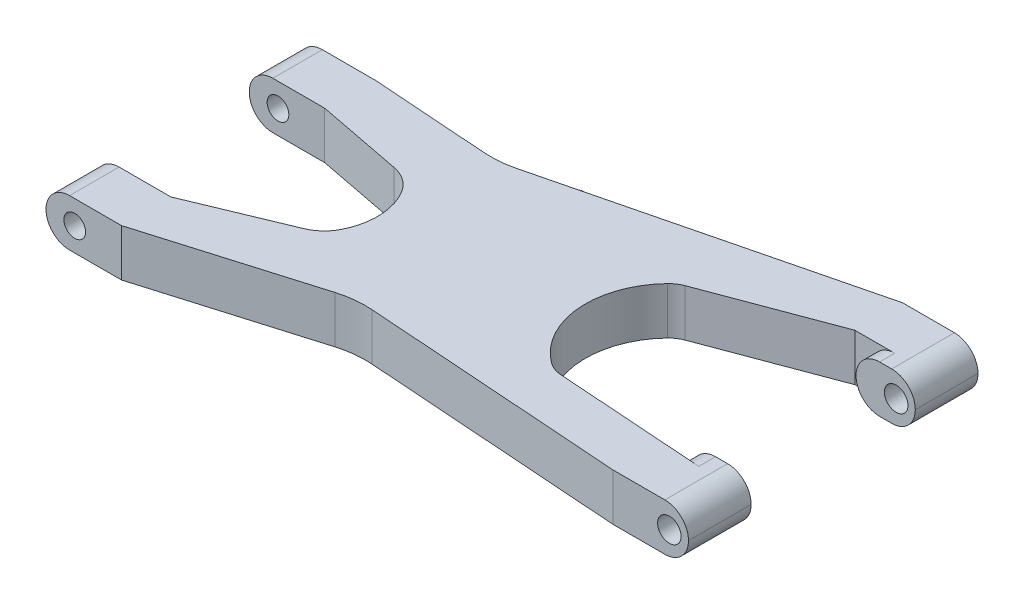
SolidWorks part; units mm, degrees
ref_plane "Front Plane" through (0, 0, 0) normal (0, 0, 1) x (1, 0, 0)
ref_plane "Top Plane" through (0, 0, 0) normal (0, 1, 0) x (1, 0, 0)
ref_plane "Right Plane" through (0, 0, 0) normal (1, 0, 0) x (0, 0, -1)
sketch "Sketch1" plane through (0, 0, 0) normal (0, 1, 0) x (1, 0, 0)
  line L0 (0, 0) -> (0, 38.989)
  line L1 (-81.915, 29.4386) -> (-71.628, 29.4386)
  line L2 (-81.915, 29.4386) -> (-81.915, -4.5974)
  line L3 (0, 0) -> (-10.16, 0)
  line L4 (-71.628, 29.4386) -> (-10.16, 38.989)
  line L5 (0, 38.989) -> (-10.16, 38.989)
  line L6 (-71.755, -4.5974) -> (-10.16, 0)
  line L8 (-81.915, -4.5974) -> (-71.755, -4.5974)
  dimension "D1" = 38.989
  dimension "D2" = 34.036
  dimension "D3" = 81.915
  dimension "D4" = 9.5504
  dimension "D5" = 4.5974
  dimension "D6" = 61.468
  dimension "D7" = 10.16
  dimension "D8" = 10.16
  dimension "D9" = 10.16
  dimension "D10" = 61.595
extrude "Boss-Extrude1" add sketch "Sketch1" along normal blind 6.35
fillet "Fillet2" radius 3.175 4 edges at (0, 0, -19.4945) (0, 6.35, -19.4945) (-81.915, 0, -12.4206) (-81.915, 6.35, -12.4206)
sketch "Sketch2" plane through (-0.605, 0, 0) normal (0, 0, -1) x (-1, 0, 0)
  circle A0 centre (1.9663, 3.175) radius 1.5875
  circle A1 centre (77.4406, 3.175) radius 1.4605
  dimension "D1" = 2.921
  dimension "D2" = 3.175
extrude "Cut-Extrude2" cut sketch "Sketch2" along normal through all and the other way through all
sketch "Sketch3" plane through (0, 0, 0) normal (0, 1, 0) x (1, 0, 0)
  line L0 (-81.915, 22.7711) -> (-71.755, 22.7711)
  line L1 (0, 30.5435) -> (0, 8.4455)
  line L2 (-10.668, 19.4945) -> (-35.4657, 19.4945) construction
  line L3 (-81.915, 22.7711) -> (-81.915, 2.0701)
  line L4 (-71.755, 2.0701) -> (-81.915, 2.0701)
  line L5 (-71.755, 22.7711) -> (-58.4876, 20.2076)
  line L6 (-71.114, 12.4206) -> (-37.8214, 12.4206) construction
  line L7 (0, 30.5435) -> (-7.9756, 30.5435)
  line L8 (-7.9756, 30.5435) -> (-7.9756, 32.5755)
  line L9 (-7.9756, 8.4455) -> (0, 8.4455)
  line L10 (-71.755, 2.0701) -> (-57.7774, 7.8837)
  line L11 (-7.9756, 8.4455) -> (-7.9756, 6.4135)
  line L12 (-7.9756, 32.5755) -> (-10.16, 32.5755)
  line L13 (-7.9756, 6.4135) -> (-24.7644, 7.5875)
  line L14 (-10.16, 32.5755) -> (-26.7956, 26.3446)
  arc A0 (-58.4876, 20.2076) -> (-57.7774, 7.8837) centre (-64.2945, 13.6906) cw
  arc A1 (-26.7699, 8.3292) -> (-28.2109, 25.4119) centre (-19.956, 17.5061) cw
  arc A2 (-24.7644, 7.5875) -> (-26.7699, 8.3292) centre (-24.4986, 11.3882) cw
  arc A3 (-26.7956, 26.3446) -> (-28.2109, 25.4119) centre (-25.4593, 22.7767) ccw
  point P18 (-25.7556, 7.6568)
  point P27 (-27.524, 26.0718)
  dimension "D9" = 12.3444
  dimension "D13" = 2.1844
  dimension "D10" = 13.5128
  dimension "D12" = 2.032
  dimension "D19" = 3.81
  dimension "D20" = 11.43
  dimension "D1" = 20.701
  dimension "D3" = 6.6675
  dimension "D4" = 10.16
  dimension "D5" = 22.098
  dimension "D6" = 8.4455
  dimension "D7" = 8.4455
  dimension "D8" = 7.9756
  dimension "D11" = 18.415
  dimension "D14" = 2.032
  dimension "D15" = 18.542
  dimension "D16" = 15.1384
  dimension "D17" = 17.78
  dimension "D18" = 86
  dimension "D21" = 6.6675
extrude "Cut-Extrude5" cut sketch "Sketch3" along normal through all
sketch "Sketch5" plane through (0, 6.35, 0) normal (0, 1, 0) x (1, 0, 0)
  line L0 (-10.16, 38.989) -> (-53.7874, 28.1798)
  line L1 (-53.7874, 28.1798) -> (-71.628, 29.4386)
  line L2 (-71.628, 29.4386) -> (-10.16, 38.989)
  line L3 (-10.16, 0) -> (-47.3941, 2.6271)
  line L4 (-47.3941, 2.6271) -> (-71.755, -4.5974)
  line L5 (-71.755, -4.5974) -> (-10.16, 0)
extrude "Cut-Extrude7" cut sketch "Sketch5" against normal blind 25.4
fillet "Fillet3" radius 3.175 4 edges at (-7.9756, 0, -7.4295) (-7.9756, 6.35, -7.4295) (-7.9756, 0, -31.5595) (-7.9756, 6.35, -31.5595)
ref_plane "Plane1" through (0, 0, -31.75) normal (0, 0, 1) x (1, 0, 0)
sketch "Sketch6" plane through (0, 0, -31.75) normal (0, 0, 1) x (1, 0, 0)
  line L0 (-45.72, 3.1087) -> (-42.164, 3.1087) construction
  line L1 (-45.72, 5.0975) -> (-42.164, 5.0975)
  line L2 (-45.72, 1.1199) -> (-42.164, 1.1199)
  line L4 (-10.16, 6.35) -> (-10.16, 0) construction
  arc A0 (-45.72, 5.0975) -> (-45.72, 1.1199) centre (-45.72, 3.1087) ccw
  arc A1 (-42.164, 1.1199) -> (-42.164, 5.0975) centre (-42.164, 3.1087) ccw
  circle A2 centre (-45.72, 3.1087) radius 1.2065
  circle A3 centre (-42.164, 3.1087) radius 1.2065
  point P2 (-43.942, 3.1087)
  point P11 (-10.16, 3.175)
  dimension "D1" = 3.556
  dimension "D2" = 2.413
  dimension "D3" = 2.413
  dimension "D4" = 32.004
extrude "Boss-Extrude2" add sketch "Sketch6" along normal blind 12.7 separate body
sketch "Sketch7" plane through (0, 0, -31.75) normal (0, 0, -1) x (-1, 0, 0)
  circle A0 centre (45.72, 3.1087) radius 1.2065
  circle A1 centre (42.164, 3.1087) radius 1.2065
  dimension "D1" = 2.413
  dimension "D2" = 2.413
extrude "Cut-Extrude8" cut sketch "Sketch7" against normal blind 12.7
fillet "Fillet5" radius 12.7 2 edges at (-53.7874, 3.175, -28.1798) (-47.3941, 3.175, -2.6271)
fillet "Fillet6" radius 5.08 2 edges at (-57.7774, 3.175, -7.8837) (-58.4876, 3.175, -20.2076)
